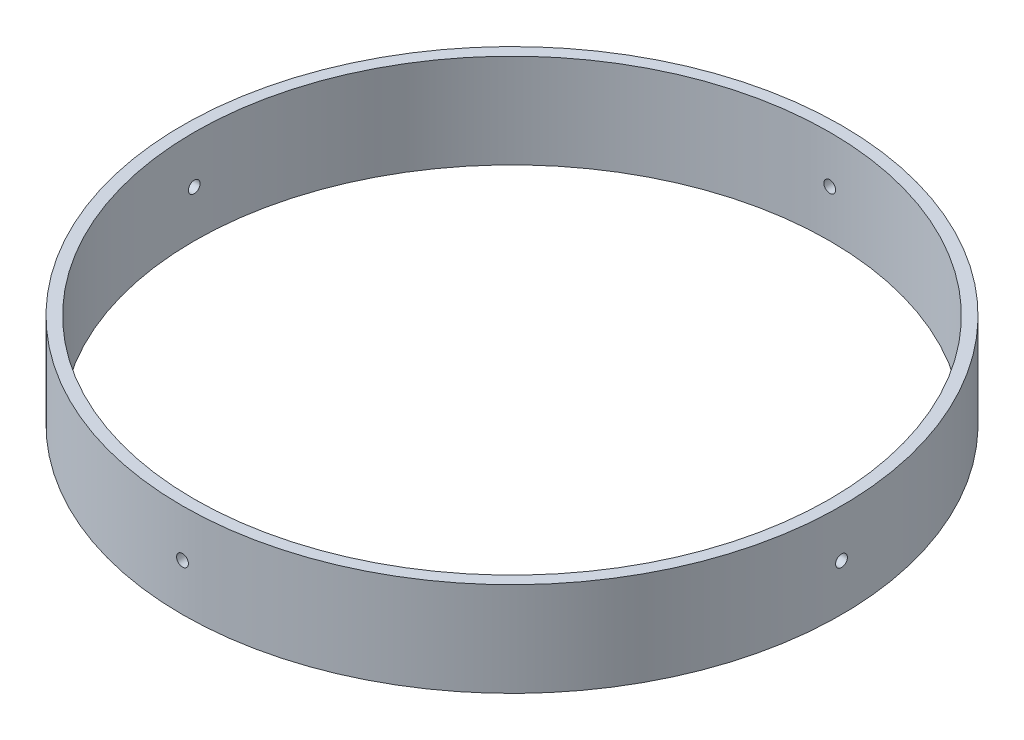
SolidWorks part; units mm, degrees
ref_plane "Front Plane" through (0, 0, 0) normal (0, 0, 1) x (1, 0, 0)
ref_plane "Top Plane" through (0, 0, 0) normal (0, 1, 0) x (1, 0, 0)
ref_plane "Right Plane" through (0, 0, 0) normal (1, 0, 0) x (0, 0, -1)
sketch "Sketch1" plane through (0, 0, 0) normal (0, 1, 0) x (1, 0, 0)
  circle A0 centre (0, 0) radius 88.9
  circle A1 centre (0, 0) radius 85.725
  dimension "D1" = 177.8
  dimension "D2" = 171.45
extrude "Boss-Extrude1" add sketch "Sketch1" along normal blind 25.4
ref_plane "Plane1" through (0, 0, 88.9) normal (0, 0, 1) x (1, 0, 0)
sketch "Sketch2" plane through (0, 0, 88.9) normal (0, 0, 1) x (1, 0, 0)
  line L0 (-88.9, 0) -> (88.9, 0) construction
  circle A0 centre (0, 12.7) radius 1.5875
  dimension "D1" = 3.175
  dimension "D2" = 12.7
extrude "Cut-Extrude1" cut sketch "Sketch2" against normal through all both and the other way through all
ref_plane "Plane2" through (88.9, 0, 0) normal (1, 0, 0) x (0, 0, -1)
sketch "Sketch3" plane through (88.9, 0, 0) normal (1, 0, 0) x (0, 0, -1)
  circle A0 centre (0, 12.5989) radius 1.5875
extrude "Cut-Extrude2" cut sketch "Sketch3" against normal through all both and the other way through all
